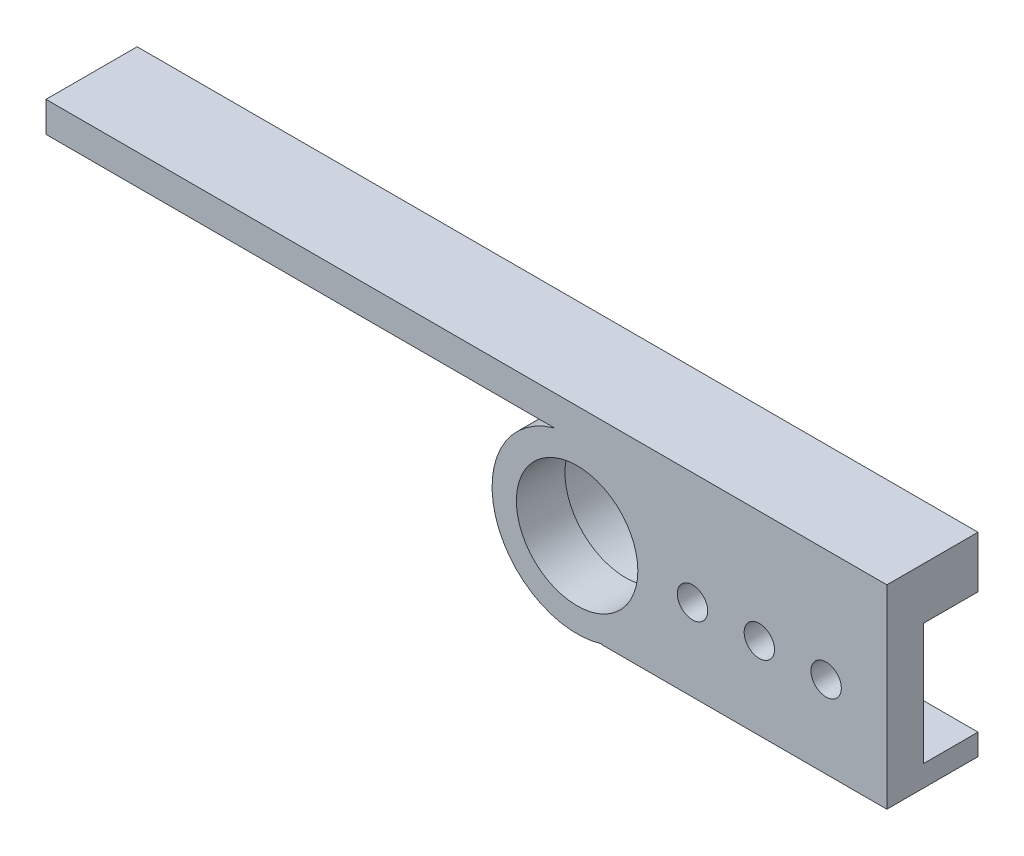
SolidWorks part; units mm, degrees
ref_plane "前视基准面" through (0, 0, 0) normal (0, 0, 1) x (1, 0, 0)
ref_plane "上视基准面" through (0, 0, 0) normal (0, 1, 0) x (1, 0, 0)
ref_plane "右视基准面" through (0, 0, 0) normal (1, 0, 0) x (0, 0, -1)
sketch "草图1" plane through (0, 0, 0) normal (0, 0, 1) x (1, 0, 0)
  line L1 (20, -10) -> (-20, -10)
  line L2 (20, -10) -> (20, 10)
  line L3 (20, 10) -> (-20, 10)
  line L4 (-20, -10) -> (-20, 10)
  line L5 (20, -10) -> (-20, 10) construction
  line L6 (20, 10) -> (-20, -10) construction
  point P0 (0, 0)
  dimension "D1" = 40
  dimension "D2" = 20
extrude "凸台-拉伸1" add sketch "草图1" along normal blind 6
sketch "草图2" plane through (0, 0, 6) normal (0, 0, 1) x (1, 0, 0)
  line L0 (20, -10) -> (20, 10) construction
  circle A0 centre (10, 0) radius 2.5
  circle A1 centre (-1, 0) radius 2.5
  circle A2 centre (-12, 0) radius 2.5
  dimension "D1" = 10
  dimension "D2" = 5
  dimension "D3" = 3
extrude "切除-拉伸1" cut sketch "草图2" against normal through all
sketch "草图3" plane through (0, 0, 6) normal (0, 0, 1) x (1, 0, 0)
  line L0 (20, 13.5) -> (20, 10)
  line L1 (20, -13.5) -> (-26.894, -13.5)
  line L3 (20, 13.5) -> (-26.894, 13.5)
  line L4 (-20, 10) -> (-20, -10)
  line L5 (-20, -10) -> (20, -10)
  line L6 (20, -10) -> (20, 10)
  line L7 (20, 10) -> (-20, 10)
  line L8 (-20, 10) -> (-20, -10)
  line L9 (-20, -10) -> (20, -10)
  line L10 (20, -10) -> (20, 10)
  line L11 (20, 10) -> (-20, 10)
  line L12 (-26.894, -13.5) -> (-26.894, 13.5)
  line L13 (20, -10.0394) -> (-26.894, 13.5) construction
  line L14 (20, 10.0394) -> (-26.894, -13.5) construction
  line L15 (20, -10) -> (20, -13.5)
  circle A0 centre (-31, 0) radius 11
  circle A1 centre (-31, 0) radius 14
  point P2 (0, 0)
  line M10 (-20, 10) -> (-20, -10)
  line M11 (-20, -10) -> (20, -10)
  line M13 (20, 10) -> (-20, 10)
  dimension "D3" = 22
  dimension "D4" = 28
  dimension "D2" = 3.5
  dimension "D1" = 0
extrude "凸台-拉伸2" add sketch "草图3" against normal blind 15 contours L3 A1 L1 L12 A0 | A1 L1 L15 M11 M10 | L1 A1 L8 A0 L12 | L8 A1 L3 L12 A0 | L8 A1 | A1 L0 L3 M10 M13 region at (-1.9449, 11.7771, 6) region at (-1.9449, -11.7771, 6) region at (-23.0173, 9.0328, 6) region at (-27.2274, 11.7946, 6) region at (-18.7882, 0, 6) region at (-23.0173, -9.0328, 6)
sketch "草图5" plane through (0, 0, 6) normal (0, 0, 1) x (1, 0, 0)
  circle A0 centre (-31, 0) radius 10
  circle A1 centre (-31, 0) radius 11 construction
  circle A2 centre (-31, 0) radius 11
  dimension "D1" = 20
extrude "凸台-拉伸3" add sketch "草图5" against normal blind 8
sketch "草图6" plane through (0, 0, 6) normal (0, 0, 1) x (1, 0, 0)
  circle A0 centre (-31, 0) radius 8.5
  circle A1 centre (-31, 0) radius 10 construction
  circle A2 centre (-31, 0) radius 10
  dimension "D1" = 17
sketch "草图7" plane through (0, 13.5, 0) normal (0, 1, 0) x (1, 0, 0)
  circle A0 centre (-16.8213, 3.0525) radius 3.3366
sketch "草图8" plane through (20, 0, 0) normal (1, 0, 0) x (0, 0, -1)
  line L1 (-6, 13.5) -> (9, 13.5)
  line L2 (-6, 13.5) -> (-6, 18.5)
  line L3 (-6, 18.5) -> (9, 18.5)
  line L4 (9, 13.5) -> (9, 18.5)
  dimension "D1" = 5
extrude "凸台-拉伸4" add sketch "草图8" against normal blind 200
sketch "草图9" plane through (0, 0, 6) normal (0, 0, 1) x (1, 0, 0)
  line L1 (-29.5663, 15.6648) -> (-25.1627, 15.6648)
  line L2 (-29.5663, 15.6648) -> (-29.5663, 11.9284)
  line L3 (-29.5663, 11.9284) -> (-25.1627, 11.9284)
  line L4 (-25.1627, 15.6648) -> (-25.1627, 11.9284)
extrude "凸台-拉伸5" add sketch "草图9" against normal through all
sketch "草图11" plane through (0, 18.5, 0) normal (0, 1, 0) x (1, 0, 0)
  line L0 (-118.4338, -6) -> (-118.4338, 9)
  line L1 (-180, -6) -> (20, -6) construction
  line L2 (-118.4338, 241.5018) -> (-118.4338, -128.4982) construction
  line L3 (-180, 9) -> (20, 9) construction
sketch "草图13" plane through (0, 18.5, 0) normal (0, 1, 0) x (1, 0, 0)
  line L1 (-118.4338, -6) -> (-183.1111, -6)
  line L2 (-118.4338, -6) -> (-118.4338, 12.5245)
  line L3 (-118.4338, 12.5245) -> (-183.1111, 12.5245)
  line L4 (-183.1111, -6) -> (-183.1111, 12.5245)
extrude "切除-拉伸2" cut sketch "草图13" against normal through all
